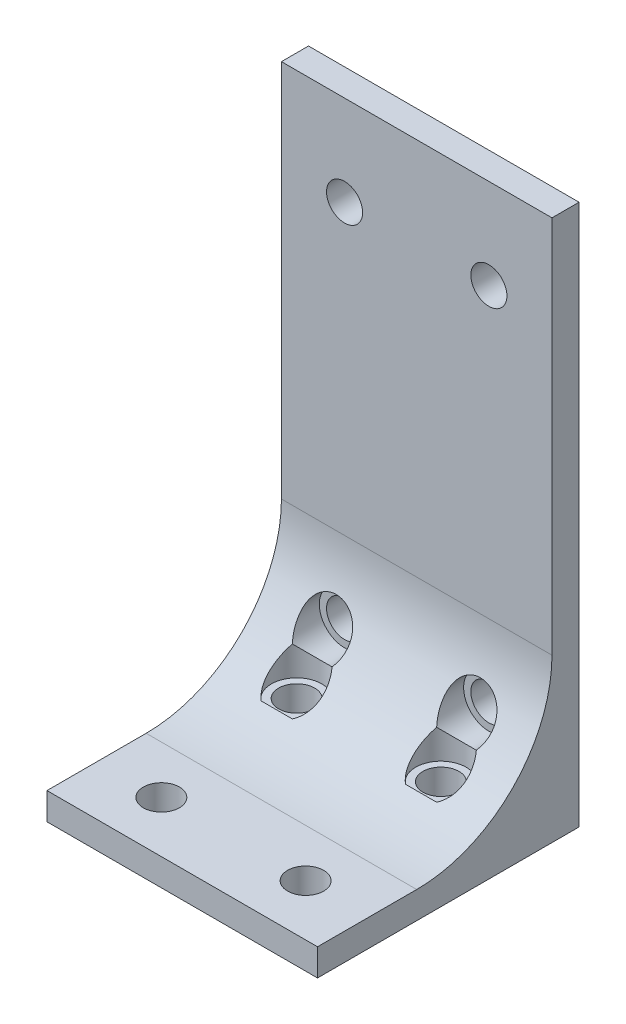
SolidWorks part; units mm, degrees
ref_plane "Front Plane" through (0, 0, 0) normal (0, 0, 1) x (1, 0, 0)
ref_plane "Top Plane" through (0, 0, 0) normal (0, 1, 0) x (1, 0, 0)
ref_plane "Right Plane" through (0, 0, 0) normal (1, 0, 0) x (0, 0, -1)
sketch "Sketch1" plane through (0, 0, 0) normal (0, 0, 1) x (1, 0, 0)
  line L0 (0, 30) -> (0, -30) construction
  line L1 (15, 30) -> (-15, 30)
  line L2 (15, 30) -> (15, -30)
  line L3 (15, -30) -> (-15, -30)
  line L4 (-15, 30) -> (-15, -30)
  line L5 (15, 30) -> (-15, -30) construction
  line L6 (15, -30) -> (-15, 30) construction
  line L7 (15, 0) -> (-15, 0) construction
  circle A0 centre (8, 20) radius 2
  circle A1 centre (8, -20) radius 2
  circle A2 centre (-8, 20) radius 2
  circle A3 centre (-8, -20) radius 2
  point P0 (0, 0)
  dimension "D3" = 4
  dimension "D1" = 60
  dimension "D2" = 30
  dimension "D4" = 8
  dimension "D5" = 20
extrude "Boss-Extrude1" add sketch "Sketch1" along normal blind 3
sketch "Sketch2" plane through (0, 0, 0) normal (1, 0, 0) x (0, 0, -1)
  line L1 (-3, -30) -> (-29, -30)
  line L2 (-3, -30) -> (-3, -27)
  line L3 (-3, -27) -> (-29, -27)
  line L4 (-29, -30) -> (-29, -27)
  dimension "D1" = 3
  dimension "D2" = 26
extrude "Boss-Extrude2" add sketch "Sketch2" along normal mid plane 30
sketch "Sketch3" plane through (0, -27, 0) normal (0, 1, 0) x (1, 0, 0)
  line L0 (0, 0) -> (0, -29) construction
  line L1 (15, -29) -> (-15, -29) construction
  line L2 (15, -3) -> (-15, -3) construction
  circle A0 centre (-8, -8.3154) radius 2
  circle A1 centre (8, -8.3154) radius 2
  circle A2 centre (-8, -23.3154) radius 2
  circle A3 centre (8, -23.3154) radius 2
  point P15 (0, 0)
  point P16 (0, 0)
  dimension "D1" = 4
  dimension "D4" = 4
  dimension "D5" = 4
  dimension "D2" = 5.3154
  dimension "D3" = 8
  dimension "D6" = 15
  dimension "D7" = 15
extrude "Cut-Extrude1" cut sketch "Sketch3" against normal through all
fillet "Fillet1" radius 15 1 edges at (0, -27, 3)
sketch "Sketch4" plane through (0, -27, 0) normal (0, 1, 0) x (1, 0, 0)
  circle A2 centre (-8, -8.3154) radius 2.8
  circle A3 centre (8, -8.3154) radius 2.8
  dimension "D1" = 5.6
extrude "Cut-Extrude2" cut sketch "Sketch4" along normal through all from offset 2
sketch "Sketch5" plane through (0, 0, 3) normal (0, 0, 1) x (1, 0, 0)
  circle A0 centre (-8, -20) radius 2.8
  circle A1 centre (8, -20) radius 2.8
  dimension "D1" = 5.6
extrude "Cut-Extrude3" cut sketch "Sketch5" along normal through all from offset 0
